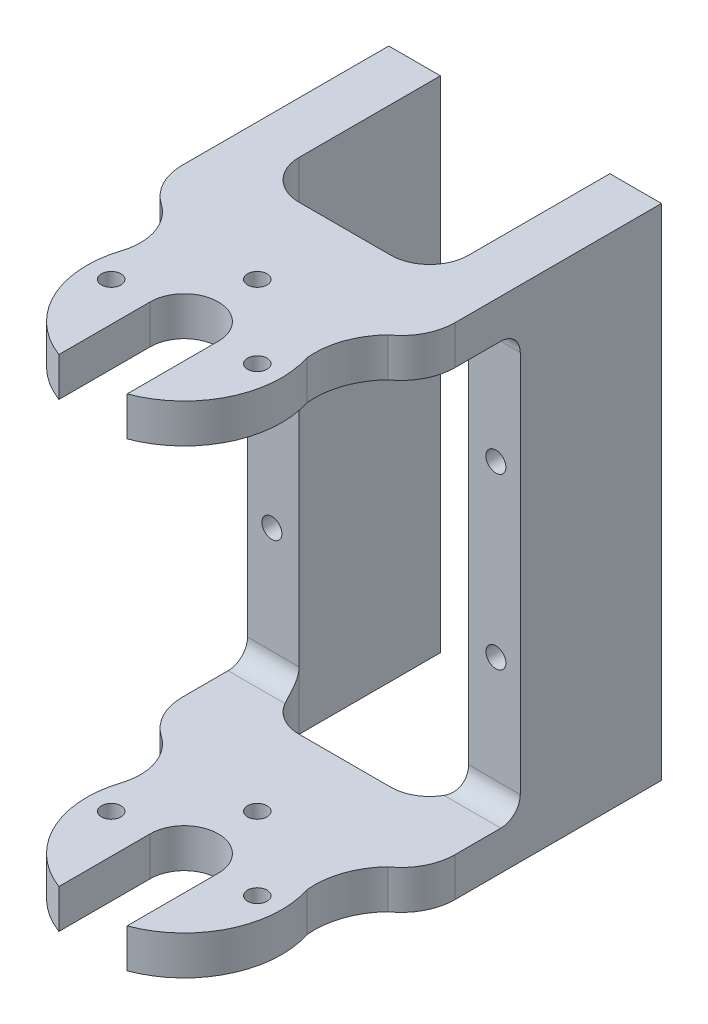
SolidWorks part; units mm, degrees
material "7075-T6 (SN)"
ref_plane "Face" through (0, 0, 0) normal (0, 0, 1) x (1, 0, 0)
ref_plane "Dessus" through (0, 0, 0) normal (0, 1, 0) x (1, 0, 0)
ref_plane "Droite" through (0, 0, 0) normal (1, 0, 0) x (0, 0, -1)
sketch "Esquisse3" plane through (0, 0, 0) normal (0, 1, 0) x (1, 0, 0)
  line L0 (-14, 0) -> (-14, -35)
  line L1 (0, 0) -> (0, -35) construction
  line L3 (14, -35) -> (14, 0)
  line L4 (-14, 0) -> (14, 0)
  line L6 (-14, 0) -> (-14, 3.841) construction
  line L7 (14, 0) -> (14, 6.0564) construction
  circle A0 centre (0, -35) radius 3.5
  arc A1 (-14, -35) -> (14, -35) centre (0, -35) ccw
  dimension "D2" = 7
  dimension "D1" = 28
  dimension "D4" = 35
extrude "Boss.-Extru.1" add sketch "Esquisse3" along normal mid plane 51.3
sketch "Esquisse5" plane through (0, 0, 0) normal (1, 0, 0) x (0, 0, -1)
  line L1 (-49, 21.65) -> (-24.5, 21.65)
  line L6 (-24.5, 21.65) -> (-24.5, -21.65)
  line L7 (-24.5, -21.65) -> (-49, -21.65)
  line L8 (-49, 25.65) -> (-49, -25.65) construction
  line L9 (-49, -21.65) -> (-49, 21.65)
  line L10 (-35, 25.65) -> (-49, 25.65) construction
  line L11 (-49, -25.65) -> (-35, -25.65) construction
  dimension "D1" = 4
  dimension "D2" = 4
  dimension "D3" = 24.5
extrude "Enlèv. mat.-Extru.2" cut sketch "Esquisse5" against normal through all and the other way through all
sketch "Esquisse6" plane through (0, -25.65, 0) normal (0, 1, 0) x (1, 0, 0)
  line L0 (-9, 0) -> (-9, -18) construction
  line L1 (-9, -18) -> (9, -18) construction
  line L2 (-8.7, 0) -> (-8.7, -14.5)
  line L5 (-4.7, -18.5) -> (4.7, -18.5)
  line L7 (14, -35) -> (14, 0) construction
  line L8 (9, -18) -> (9, 0) construction
  line L9 (9, 0) -> (-9, 0) construction
  line L11 (0, 0) -> (0, -37) construction
  line L12 (0, -35) -> (14, -26.9171) construction
  line L13 (-14, 0) -> (-14, -35) construction
  line L14 (8.7, -14.5) -> (8.7, 0)
  line L15 (14, 0) -> (-14, 0) construction
  line L16 (8.7, 0) -> (-8.7, 0)
  arc A0 (-8.7, -14.5) -> (-4.7, -18.5) centre (-4.7, -14.5) ccw
  arc A1 (4.7, -18.5) -> (8.7, -14.5) centre (4.7, -14.5) ccw
  point P4 (0, -18.5)
  dimension "D1" = 18
  dimension "D2" = 4
  dimension "D6" = 5.3
  dimension "D8" = 18.5
extrude "Enlèv. mat.-Extru.3" cut sketch "Esquisse6" against normal through all and the other way through all
sketch "Esquisse11" plane through (0, -25.65, 0) normal (0, -1, 0) x (1, 0, 0)
  line L0 (0, 49) -> (0, 21.2035) construction
  line L1 (-14, 0) -> (-14, 35) construction
  line L3 (14, 21.2035) -> (14, 35)
  line L4 (14, 35) -> (14, 0) construction
  line L5 (-14, 21.2035) -> (14, 21.2035) construction
  line L6 (-14, 21.2035) -> (-14, 35)
  arc A0 (9.5193, 31.9368) -> (-9.5193, 31.9368) centre (0, 35) ccw
  arc A1 (-11.6274, 25.7277) -> (-14, 21.2035) centre (-8.5, 21.2035) ccw
  arc A2 (9.5193, 31.9368) -> (11.6274, 25.7277) centre (17.3235, 31.1241) ccw
  arc A3 (14, 35) -> (-14, 35) centre (0, 35) ccw construction
  arc A4 (14, 35) -> (-14, 35) centre (0, 35) ccw
  arc A5 (-9.5193, 31.9368) -> (-11.6274, 25.7277) centre (-14.7549, 30.252) cw
  arc A6 (11.6274, 25.7277) -> (14, 21.2035) centre (8.5, 21.2035) cw
  dimension "D1" = 20
  dimension "D2" = 5.5
extrude "Enlèv. mat.-Extru.6" cut sketch "Esquisse11" against normal through all
ref_plane "Plan1" through (0, 0, 45) normal (0, 0, 1) x (1, 0, 0)
sketch "Esquisse16" plane through (0, 0, 0) normal (0, 0, -1) x (-1, 0, 0)
  line L0 (0, 23.0718) -> (0, -4.4703) construction
  line L4 (-17.4288, 0) -> (26.647, 0) construction
  circle A0 centre (-11.5, 8.7) radius 1.025
  circle A1 centre (11.5, 8.7) radius 1.025
  circle A2 centre (-11.5, -8.7) radius 1.025
  circle A3 centre (11.5, -8.7) radius 1.025
  dimension "D2" = 8.7
  dimension "D3" = 2.05
  dimension "D4" = 2.05
  dimension "D5" = 2.05
  dimension "D6" = 2.05
  dimension "D7" = 17.4
  dimension "D8" = 8.7
  dimension "D1" = 17.4
  dimension "D9" = 23
  dimension "D10" = 23
  dimension "D11" = 11.5
extrude "Enlèv. mat.-Extru.7" cut sketch "Esquisse16" against normal through all
sketch "Esquisse19" plane through (0, 0, 24.5) normal (0, 0, 1) x (1, 0, 0)
  line L0 (-12.9026, -21.65) -> (12.9026, -21.65) construction
  line L1 (-15, 21.65) -> (15, 21.65)
  line L2 (-15, 21.65) -> (-15, -21.65)
  line L3 (-15, -21.65) -> (15, -21.65)
  line L4 (15, 21.65) -> (15, -21.65)
  line L5 (-12.9026, 21.65) -> (12.9026, 21.65) construction
  line L6 (0, 10.4807) -> (0, -9.59) construction
  dimension "D1" = 30
  dimension "D2" = 15
extrude "Enlèv. mat.-Extru.11" cut sketch "Esquisse19" against normal blind 10
fillet "Congé1" radius 2 4 edges at (11.35, -21.65, 14.5) (-11.35, -21.65, 14.5) (11.35, 21.65, 14.5) (-11.35, 21.65, 14.5)
sketch "Esquisse20" plane through (0, -25.65, 0) normal (0, -1, 0) x (1, 0, 0)
  line L0 (3.5, 35) -> (3.5, 46.5217)
  line L1 (3.5, 46.5217) -> (-3.5, 46.5217)
  line L2 (-3.5, 46.5217) -> (-3.5, 35)
  line L3 (-3.5, 35) -> (3.5, 35)
  circle A0 centre (0, 35) radius 3.5 construction
extrude "Enlèv. mat.-Extru.12" cut sketch "Esquisse20" against normal through all
sketch "Esquisse22" plane through (0, -25.65, 0) normal (0, -1, 0) x (1, 0, 0)
  line L0 (0, 35) -> (0, 21.0842) construction
  line L1 (0, 35) -> (15.3618, 35) construction
  circle A0 centre (0, 27.5) radius 1
  circle A1 centre (-7.5, 35) radius 1
  circle A2 centre (0, 42.5) radius 1
  circle A3 centre (7.5, 35) radius 1
  point P16 (0, 35)
  dimension "D2" = 2
  dimension "D1" = 7.5
  dimension "D3" = 4
extrude "Enlèv. mat.-Extru.14" cut sketch "Esquisse22" against normal through all
